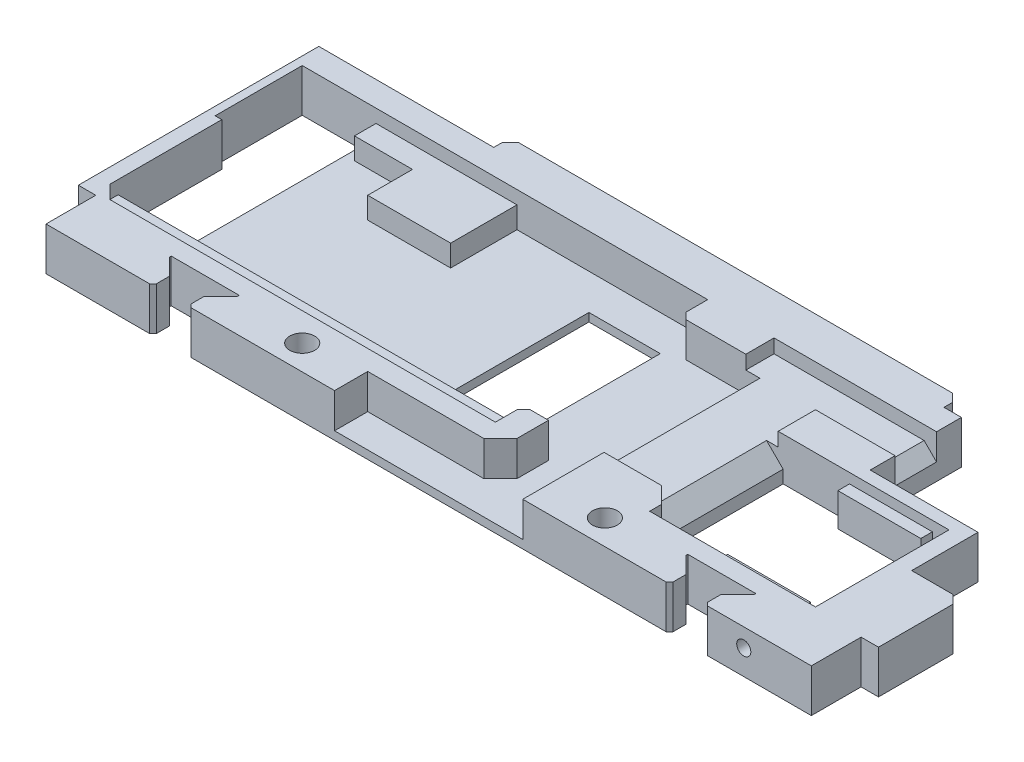
SolidWorks part; units mm, degrees
ref_plane "前视基准面" through (0, 0, 0) normal (0, 0, 1) x (1, 0, 0)
ref_plane "上视基准面" through (0, 0, 0) normal (0, 1, 0) x (1, 0, 0)
ref_plane "右视基准面" through (0, 0, 0) normal (1, 0, 0) x (0, 0, -1)
sketch "草图1" plane through (0, 0, 0) normal (0, 1, 0) x (1, 0, 0)
  line L1 (0, 0) -> (96.5, 0) construction
  line L2 (0, 0) -> (0, 35) construction
  line L3 (0, 35) -> (96.5, 35)
  line L4 (96.5, 0) -> (96.5, 35) construction
  line L5 (0, 35) -> (0, 0)
  line L7 (0, 0) -> (96.5, 0)
  line L10 (96.5, 35) -> (96.5, 0)
  dimension "D1" = 96.5
  dimension "D2" = 35
extrude "凸台-拉伸1" add sketch "草图1" along normal blind 5.2
sketch "草图4" plane through (0, 5.2, 0) normal (0, 1, 0) x (1, 0, 0)
  line L0 (0, 35) -> (0, 0) construction
  line L1 (1.8, 6.4) -> (49.9, 6.4)
  line L2 (1.8, 6.4) -> (1.8, 32)
  line L3 (1.8, 32) -> (49.9, 32)
  line L4 (49.9, 6.4) -> (49.9, 9.8)
  line L5 (0, 0) -> (96.5, 0) construction
  line L6 (49.9, 28.6) -> (49.9, 32)
  line L7 (49.9, 28.6) -> (57.9, 28.6)
  line L9 (49.9, 9.8) -> (57.9, 9.8)
  line L10 (57.9, 28.6) -> (57.9, 9.8)
  dimension "D1" = 1.8
  dimension "D2" = 6.4
  dimension "D3" = 25.6
  dimension "D4" = 48.1
  dimension "D5" = 3.4
  dimension "D6" = 3.4
  dimension "D7" = 8
extrude "切除-拉伸6" cut sketch "草图4" against normal blind 1.6
sketch "草图5" plane through (0, 3.6, 0) normal (0, 1, 0) x (1, 0, 0)
  line L0 (49.9, 9) -> (1.8, 9)
  line L3 (1.8, 6.4) -> (49.9, 6.4) construction
  line L4 (16.9, 29.4) -> (9.9, 29.4)
  line L6 (16.9, 29.4) -> (16.9, 24)
  line L7 (16.9, 24) -> (26.9, 24)
  line L8 (1.8, 32) -> (1.8, 6.4)
  line L9 (1.8, 6.4) -> (49.9, 6.4)
  line L10 (49.9, 6.4) -> (49.9, 9.8)
  line L11 (49.9, 9.8) -> (57.9, 9.8)
  line L12 (57.9, 9.8) -> (57.9, 28.6)
  line L13 (57.9, 28.6) -> (49.9, 28.6)
  line L14 (49.9, 28.6) -> (49.9, 32)
  line L15 (49.9, 32) -> (1.8, 32)
  line L16 (1.8, 32) -> (1.8, 9)
  line L18 (49.9, 9) -> (49.9, 9.8)
  line L19 (49.9, 9.8) -> (57.9, 9.8)
  line L20 (57.9, 9.8) -> (57.9, 28.6)
  line L21 (57.9, 28.6) -> (49.9, 28.6)
  line L22 (49.9, 28.6) -> (49.9, 32)
  line L23 (9.9, 32) -> (1.8, 32)
  line L24 (26.9, 32) -> (26.9, 24)
  line L25 (9.9, 29.4) -> (9.9, 32)
  line L26 (26.9, 32) -> (49.9, 32)
  dimension "D2" = 2.6
  dimension "D3" = 10
  dimension "D4" = 2.6
  dimension "D5" = 8
  dimension "D6" = 23
  dimension "D7" = 17
  dimension "D1" = 0
extrude "切除-拉伸7" cut sketch "草图5" against normal blind 2.6
sketch "草图6" plane through (0, 1, 0) normal (0, 1, 0) x (1, 0, 0)
  line L0 (3.8, 32) -> (8.8, 32)
  line L3 (1, 32) -> (1, 21.5)
  line L4 (1, 21.5) -> (1.8, 21.5)
  line L7 (3.8, 32) -> (1, 32)
  line L9 (9.9, 32) -> (1.8, 32) construction
  line L11 (0, 35) -> (0, 0) construction
  line L12 (8.8, 32) -> (8.8, 9)
  line L13 (1.8, 9) -> (49.9, 9) construction
  line L14 (1.8, 9) -> (8.8, 9)
  line L15 (1.8, 32) -> (1.8, 9) construction
  line L16 (1.8, 21.5) -> (1.8, 9)
  line L17 (49.9, 32) -> (1.8, 32) construction
  dimension "D3" = 1
  dimension "D4" = 10.5
  dimension "D5" = 7
extrude "切除-拉伸15" cut sketch "草图6" against normal mid plane 10
sketch "草图7" plane through (0, 1, 0) normal (0, 1, 0) x (1, 0, 0)
  line L1 (39.879, 27.7) -> (47.879, 27.7)
  line L2 (39.879, 27.7) -> (39.879, 10.7)
  line L3 (39.879, 10.7) -> (47.879, 10.7)
  line L4 (47.879, 27.7) -> (47.879, 10.7)
  line L5 (49.9, 32) -> (1, 32) construction
  line L6 (51.879, 32) -> (51.879, 28.19) construction
  dimension "D1" = 17
  dimension "D2" = 4.3
  dimension "D3" = 12
  dimension "D4" = 8
extrude "切除-拉伸16" cut sketch "草图7" against normal through all
sketch "草图8" plane through (0, 5.2, 0) normal (0, 1, 0) x (1, 0, 0)
  line L0 (1.8, 6.4) -> (49.9, 6.4) construction
  line L1 (70.4, 22.5) -> (88.5, 22.5)
  line L2 (70.4, 22.5) -> (70.4, 6.4)
  line L3 (70.4, 6.4) -> (88.5, 6.4)
  line L4 (88.5, 22.5) -> (88.5, 6.4)
  line L5 (49.9, 6.4) -> (49.9, 9.8) construction
  dimension "D1" = 16.1
  dimension "D2" = 18.1
  dimension "D3" = 0
  dimension "D4" = 20.5
extrude "切除-拉伸17" cut sketch "草图8" against normal blind 1.66
sketch "草图9" plane through (0, 3.54, 0) normal (0, 1, 0) x (1, 0, 0)
  line L0 (88.5, 22.5) -> (70.4, 22.5) construction
  line L1 (71.6, 22.5) -> (86.8, 22.5)
  line L2 (71.6, 22.5) -> (71.6, 6.4)
  line L3 (71.6, 6.4) -> (86.8, 6.4)
  line L4 (86.8, 22.5) -> (86.8, 6.4)
  line L5 (70.4, 6.4) -> (88.5, 6.4) construction
  line L6 (70.4, 22.5) -> (70.4, 6.4) construction
  line L7 (88.5, 6.4) -> (88.5, 22.5) construction
  dimension "D1" = 1.2
  dimension "D2" = 1.7
extrude "切除-拉伸18" cut sketch "草图9" against normal up to next
chamfer "倒角1" distance 0.6 angle 45 1 edges at (47.879, 1, -19.2)
sketch "草图10" plane through (0, 5.2, 0) normal (0, 1, 0) x (1, 0, 0)
  line L1 (70.4, 22.5) -> (57.9, 22.5)
  line L2 (70.4, 22.5) -> (70.4, 9.8)
  line L3 (70.4, 9.8) -> (57.9, 9.8)
  line L4 (57.9, 22.5) -> (57.9, 9.8)
extrude "切除-拉伸19" cut sketch "草图10" against normal up to surface (1.66 mm away) up to face at (71, 3.54, -14.45)
chamfer "倒角2" distance 0.8 angle 45 2 edges at (49.9, 3.1, -28.6) (49.9, 3.1, -9.8)
sketch "草图12" plane through (0, 5.2, 0) normal (0, 1, 0) x (1, 0, 0)
  line L1 (96.5, 35) -> (77.5, 35)
  line L2 (96.5, 35) -> (96.5, 16)
  line L3 (90.5, 24) -> (77.5, 24)
  line L4 (77.5, 35) -> (77.5, 24)
  line L7 (96.5, 16) -> (90.5, 16)
  line L8 (90.5, 24) -> (90.5, 16)
  dimension "D1" = 11
  dimension "D2" = 19
  dimension "D3" = 19
  dimension "D4" = 6
extrude "切除-拉伸20" cut sketch "草图12" against normal through all
chamfer "倒角4" distance 1 angle 45 1 edges at (96.5, 2.6, -16)
sketch "草图14" plane through (0, 5.2, 0) normal (0, 1, 0) x (1, 0, 0)
  line L0 (77.5, 35) -> (0, 35) construction
  line L1 (21.1, 35) -> (75.4, 35)
  line L2 (21.1, 35) -> (21.1, 37)
  line L3 (21.1, 37) -> (75.4, 37)
  line L4 (75.4, 35) -> (75.4, 37)
  line L5 (0, 35) -> (0, 0) construction
  line L6 (96.5, 0) -> (96.5, 15) construction
  dimension "D1" = 21.1
  dimension "D2" = 21.1
  dimension "D3" = 2
extrude "凸台-拉伸2" add sketch "草图14" against normal up to surface (5.2 mm away) up to face at (79.2, 0, -14.45)
chamfer "倒角5" distance 1 angle 45 2 edges at (75.4, 2.6, -37) (21.1, 2.6, -37)
sketch "草图15" plane through (0, 5.2, 0) normal (0, 1, 0) x (1, 0, 0)
  line L0 (77.5, 35) -> (77.5, 24) construction
  line L1 (77.5, 32) -> (57.9, 32)
  line L2 (77.5, 32) -> (77.5, 27)
  line L3 (77.5, 27) -> (67.9, 27)
  line L4 (57.9, 32) -> (57.9, 30.6025)
  line L5 (57.9, 9.8) -> (57.9, 28.6) construction
  line L6 (88.5, 22.5) -> (57.9, 22.5) construction
  line L8 (57.9, 30.6025) -> (57.9, 22.5)
  line L9 (57.9, 22.5) -> (67.9, 22.5)
  line L10 (67.9, 27) -> (67.9, 22.5)
  line L11 (77.5, 35) -> (75.4, 35) construction
  point P15 (57.9, 26.5512)
  dimension "D1" = 3
  dimension "D2" = 5
  dimension "D3" = 10
extrude "切除-拉伸21" cut sketch "草图15" against normal up to surface (1.66 mm away) up to face at (87.65, 3.54, -14.45)
chamfer "倒角3" distance 1.5 angle 45 1 edges at (77.5, 3.54, -29.5)
chamfer "倒角6" distance 1.6 angle 45 1 edges at (1.8, 4.4, -6.4)
sketch "草图16" plane through (0, 5.2, 0) normal (0, 1, 0) x (1, 0, 0)
  line L1 (0, 0) -> (2.1, 0)
  line L2 (0, 0) -> (0, 6)
  line L3 (0, 6) -> (2.1, 6)
  line L4 (2.1, 0) -> (2.1, 6)
  line L5 (96.5, 0) -> (94.4, 0)
  line L6 (96.5, 0) -> (96.5, 6)
  line L7 (96.5, 6) -> (94.4, 6)
  line L8 (94.4, 0) -> (94.4, 6)
  dimension "D1" = 6
  dimension "D2" = 2.1
extrude "切除-拉伸22" cut sketch "草图16" against normal through all
sketch "草图19" plane through (0, 5.2, 0) normal (0, 1, 0) x (1, 0, 0)
  line L0 (2.1, 0) -> (94.4, 0) construction
  line L3 (15, 0) -> (19.2, 0)
  line L5 (2.1, 0) -> (2.1, 6) construction
  line L6 (94.4, 6) -> (94.4, 0) construction
  line L7 (17.1, 8.32) -> (17.1, -2.6088) construction
  line L9 (77.3, 2) -> (77.3, 0)
  line L10 (77.3, 0) -> (81.5, 0)
  line L14 (13, 2) -> (15, 2)
  line L15 (13, 2) -> (13, 4.2)
  line L16 (13, 4.2) -> (21.2, 4.2)
  line L17 (21.2, 2) -> (21.2, 4.2)
  line L18 (13, 2) -> (21.2, 4.2) construction
  line L19 (13, 4.2) -> (21.2, 2) construction
  line L20 (75.3, 2) -> (77.3, 2)
  line L21 (75.3, 2) -> (75.3, 4.2)
  line L22 (75.3, 4.2) -> (83.5, 4.2)
  line L23 (83.5, 2) -> (83.5, 4.2)
  line L24 (75.3, 2) -> (83.5, 4.2) construction
  line L25 (75.3, 4.2) -> (83.5, 2) construction
  line L26 (79.4, -2.3924) -> (79.4, 10.1048) construction
  line L27 (15, 2) -> (15, 0)
  line L28 (19.2, 2) -> (19.2, 0)
  line L29 (19.2, 2) -> (21.2, 2)
  line L30 (81.5, 2) -> (83.5, 2)
  line L31 (81.5, 2) -> (81.5, 0)
  point P0 (24.5613, 2.8556)
  point P7 (79.4, 3.8562)
  point P12 (17.1, 3.1)
  point P17 (79.4, 3.1)
  point P26 (17.1, 2.8556)
  point P30 (79.4, 3.8562)
  dimension "D1" = 4.2
  dimension "D2" = 2.2
  dimension "D3" = 2
  dimension "D4" = 8.2
  dimension "D5" = 15
  dimension "D6" = 15
extrude "切除-拉伸24" cut sketch "草图19" against normal through all
chamfer "倒角11" distance 2 angle 45 4 edges at (83.5, 2.6, -2) (75.3, 2.6, -2) (21.2, 2.6, -2) (13, 2.6, -2)
chamfer "倒角10" distance 0.4 angle 45 4 edges at (81.5, 2.6, 0) (77.3, 2.6, 0) (15, 2.6, 0) (19.2, 2.6, 0)
sketch "草图21" plane through (0, 5.2, 0) normal (0, 1, 0) x (1, 0, 0)
  line L0 (50.7, 9.8) -> (70.4, 9.8) construction
  line L1 (52.9, 9.8) -> (59.6, 9.8)
  line L2 (52.9, 9.8) -> (52.9, 0)
  line L3 (52.9, 0) -> (59.6, 0)
  line L4 (59.6, 9.8) -> (59.6, 0)
  line L5 (19.6, 0) -> (76.9, 0) construction
  line L6 (49.9, 6.4) -> (49.9, 9) construction
  dimension "D1" = 6.7
  dimension "D2" = 3
extrude "切除-拉伸26" cut sketch "草图21" against normal up to surface (4.2 mm away) up to face at (44.179, 1, -19.2)
chamfer "倒角9" distance 1.7 angle 45 2 edges at (57.9, 3.54, -19.2) (58.75, 3.54, -9.8)
sketch "草图22" plane through (0, 5.2, 0) normal (0, 1, 0) x (1, 0, 0)
  line L1 (52.9, 0) -> (36.9, 0)
  line L2 (52.9, 0) -> (52.9, 4)
  line L3 (52.9, 4) -> (36.9, 4)
  line L4 (36.9, 0) -> (36.9, 4)
  dimension "D1" = 16
  dimension "D2" = 4
extrude "切除-拉伸27" cut sketch "草图22" against normal up to surface (4.2 mm away) up to face at (44.179, 1, -19.2)
chamfer "倒角12" distance 2 angle 45 1 edges at (52.9, 3.1, -4)
sketch "草图24" plane through (0, 5.2, 0) normal (0, 1, 0) x (1, 0, 0)
  circle A0 centre (66.5, 3) radius 1.2 construction
  circle A1 centre (30, 3) radius 1.2 construction
  circle A2 centre (66.5, 3) radius 1.2 construction
  circle A3 centre (30, 3) radius 1.2 construction
  circle A4 centre (30, 3) radius 1.5
  circle A5 centre (66.5, 3) radius 1.5
  dimension "D1" = 3
extrude "切除-拉伸28" cut sketch "草图24" against normal through all
sketch "草图25" plane through (0, 0, -35) normal (0, 0, -1) x (-1, 0, 0)
  circle A0 centre (-10.2, 2.6) radius 1.2 construction
  circle A1 centre (-10.2, 2.6) radius 1.2 construction
  circle A2 centre (-10.2, 2.6) radius 0.85
  dimension "D1" = 1.7
extrude "切除-拉伸29" cut sketch "草图25" against normal blind 3
sketch "草图26" plane through (0, 0, 0) normal (0, 0, 1) x (1, 0, 0)
  circle A0 centre (86.25, 3) radius 1.2 construction
  circle A1 centre (86.25, 3) radius 1.2 construction
  circle A2 centre (86.25, 3) radius 0.85
  dimension "D1" = 1.7
extrude "切除-拉伸30" cut sketch "草图26" against normal blind 4
sketch "草图27" plane through (0, 5.2, 0) normal (0, 1, 0) x (1, 0, 0)
  line L0 (70.4, 6.4) -> (88.5, 6.4) construction
  line L1 (88.5, 22.5) -> (68.5, 22.5)
  line L2 (88.5, 22.5) -> (88.5, 6.4)
  line L3 (88.5, 6.4) -> (68.5, 6.4)
  line L4 (68.5, 22.5) -> (68.5, 6.4)
  dimension "D1" = 20
extrude "切除-拉伸31" cut sketch "草图27" against normal through all
sketch "草图28" plane through (0, 0, 0) normal (0, -1, 0) x (1, 0, 0)
  line L0 (88.5, -6.4) -> (68.5, -6.4) construction
  line L1 (76.5, -6.4) -> (86.5, -6.4)
  line L2 (76.5, -6.4) -> (76.5, -7.8)
  line L3 (76.5, -7.8) -> (86.5, -7.8)
  line L4 (86.5, -6.4) -> (86.5, -7.8)
  line L5 (68.5, -22.5) -> (88.5, -22.5) construction
  line L6 (86.5, -22.5) -> (76.5, -22.5)
  line L7 (86.5, -22.5) -> (86.5, -21.1)
  line L8 (86.5, -21.1) -> (76.5, -21.1)
  line L9 (76.5, -22.5) -> (76.5, -21.1)
  line L10 (88.5, -6.4) -> (88.5, -22.5) construction
  dimension "D1" = 2
  dimension "D2" = 1.4
  dimension "D3" = 10
extrude "凸台-拉伸3" add sketch "草图28" against normal blind 4
chamfer "倒角13" distance 2 angle 45 1 edges at (68.5, 4.37, -9.8)
chamfer "倒角14" distance 2 angle 45 1 edges at (68.5, 3.54, -15.15)
equation "\"0，8\"=1"
